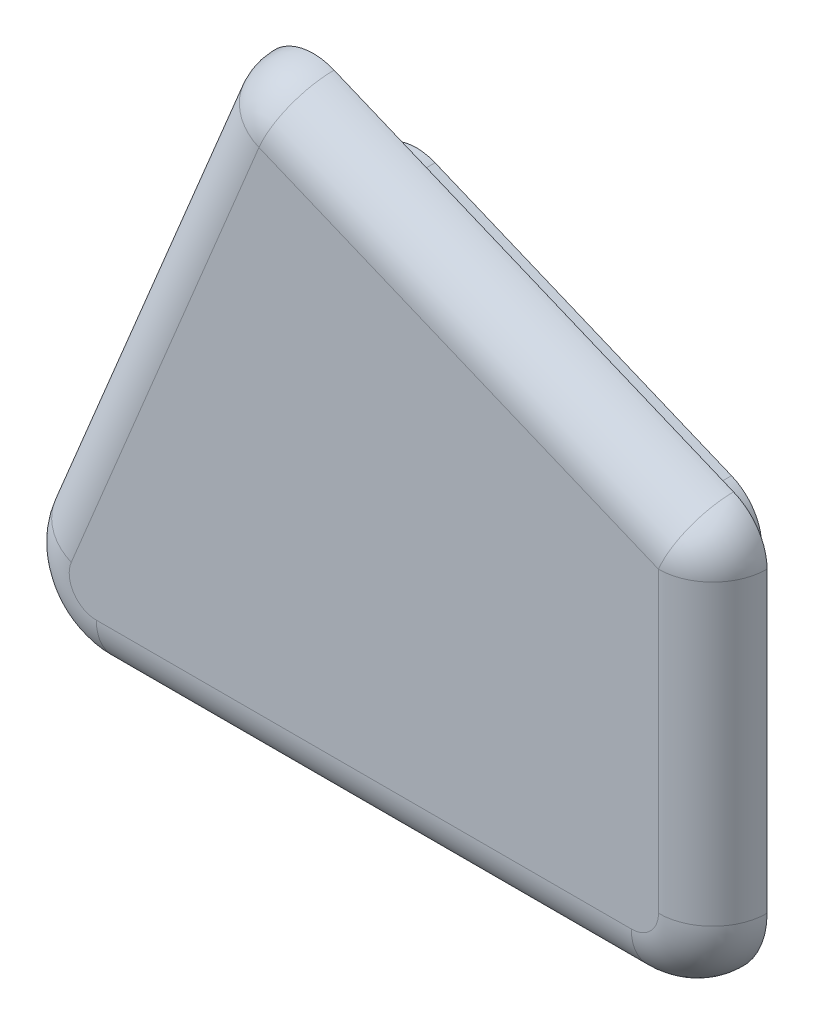
SolidWorks part; units mm, degrees
note: The reader was unsure of these and kept them because the rebuilt part matched: shared geometry of "Sketch1<4>".
ref_plane "Front Plane" through (0, 0, 0) normal (0, 0, 1) x (1, 0, 0)
ref_plane "Top Plane" through (0, 0, 0) normal (0, 1, 0) x (1, 0, 0)
ref_plane "Right Plane" through (0, 0, 0) normal (1, 0, 0) x (0, 0, -1)
sketch "Sketch1" plane through (0, 0, 0) normal (0, 0, 1) x (1, 0, 0)
  line L0 (26.646, 31.5931) -> (26.646, 15)
  line L1 (-19.9794, 8) -> (19.646, 8)
  line L2 (-22.751, 12.1481) -> (-9.3011, 44.619)
  line L3 (-3.4216, 47.0543) -> (23.8681, 35.7506)
  line L8 (29.0594, 39.5534) -> (-7.7185, 54.7873)
  line L9 (-14.2513, 52.0814) -> (-31.5287, 10.3701)
  line L10 (-24.5996, 0) -> (24.646, 0)
  line L11 (32.146, 7.5) -> (32.146, 34.934)
  line L12 (-23.213, 12.3394) -> (-9.7631, 44.8103) construction
  line L13 (-19.9794, 7.5) -> (19.646, 7.5) construction
  line L14 (27.146, 31.5931) -> (27.146, 15) construction
  line L15 (-3.2303, 47.5163) -> (24.0594, 36.2125) construction
  arc A0 (19.646, 8) -> (26.646, 15) centre (19.646, 15) ccw
  arc A1 (-22.751, 12.1481) -> (-19.9794, 8) centre (-19.9794, 11) ccw
  arc A2 (-3.4216, 47.0543) -> (-9.3011, 44.619) centre (-5.1437, 42.8969) ccw
  arc A3 (26.646, 31.5931) -> (23.8681, 35.7506) centre (22.146, 31.5931) ccw
  arc A8 (-7.7185, 54.7873) -> (-14.2513, 52.0814) centre (-9.6319, 50.1679) ccw
  arc A9 (-31.5287, 10.3701) -> (-24.5996, 0) centre (-24.5996, 7.5) ccw
  arc A10 (24.646, 0) -> (32.146, 7.5) centre (24.646, 7.5) ccw
  arc A11 (32.146, 34.934) -> (29.0594, 39.5534) centre (27.146, 34.934) ccw
  arc A12 (-3.2303, 47.5163) -> (-9.7631, 44.8103) centre (-5.1437, 42.8969) ccw construction
  arc A13 (-23.213, 12.3394) -> (-19.9794, 7.5) centre (-19.9794, 11) ccw construction
  arc A14 (19.646, 7.5) -> (27.146, 15) centre (19.646, 15) ccw construction
  arc A15 (27.146, 31.5931) -> (24.0594, 36.2125) centre (22.146, 31.5931) ccw construction
  dimension "D1" = 0.5
extrude "Boss-Extrude1" add sketch "Sketch1" along normal blind 5 contours L14 A15 L15 A12 L12 A13 L13 A14 | L11 A11 L8 A8 L9 A9 L10 A10 A15 L14 A14 L13 A13 L12 A12 L15 | L0 A3 L3 A2 L2 A1 L1 A0
extrude "Boss-Extrude2" add sketch "Sketch1<4>" against normal blind 5 contours L14 A15 L15 A12 L12 A13 L13 A14 | L0 A3 L3 A2 L2 A1 L1 A0
sketch "Sketch1<4>" plane through (0, 0, 0) normal (0, 0, 1) x (1, 0, 0) same geometry as "Sketch1"
sketch3d "3DSketch3"
  point P0 (26.646, 24.4461, -1.811)
other "Snap Hook3" [suppressed] parameters "BaseDepth"=2, "TopDepth"=2, "Width"=4, "HookHeight"=6, "Overhang"=2, "BodyHeight"=10, "Draft"=3, "LipHeight"=0
sketch3d "3DSketch7"
  point P0 (0.6818, 45.3547, -1.6871)
other "Snap Hook7" [suppressed] parameters "BaseDepth"=2, "TopDepth"=2, "Width"=4, "HookHeight"=6, "Overhang"=2, "BodyHeight"=10, "Draft"=3, "LipHeight"=0
sketch3d "3DSketch9"
  point P0 (-21.7005, 14.6844, -2.5852)
other "Snap Hook9" [suppressed] parameters "BaseDepth"=2, "TopDepth"=2, "Width"=4, "HookHeight"=6, "Overhang"=2, "BodyHeight"=10, "Draft"=3, "LipHeight"=0
fillet "Fillet1" radius 5 8 edges at (29.9493, 2.1967, 5) (0.0232, 0, 5) (-30.8356, 3.3332, 5) (-22.89, 31.2257, 5) (-11.5453, 54.7873, 5) (10.6705, 47.1704, 5) (31.3034, 37.7119, 5) (32.146, 21.217, 5)
